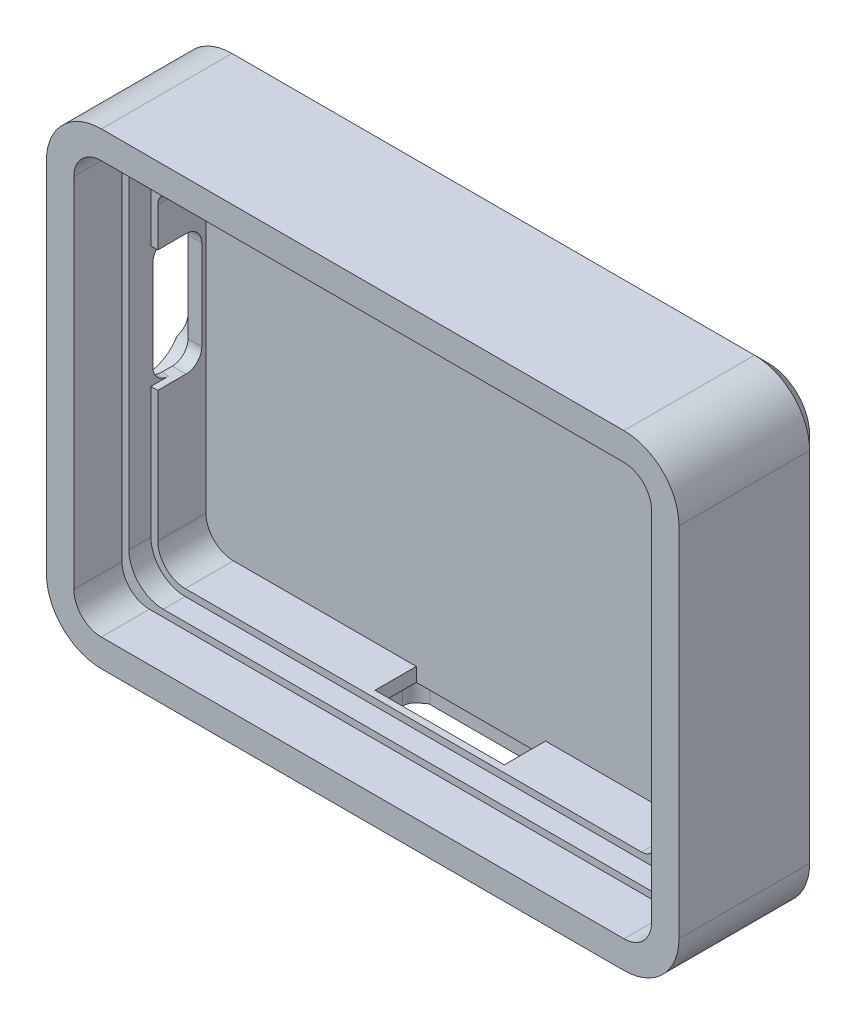
SolidWorks part; units mm, degrees
material "ABS"
ref_plane "前视基准面" through (0, 0, 0) normal (0, 0, 1) x (1, 0, 0)
ref_plane "上视基准面" through (0, 0, 0) normal (0, 1, 0) x (1, 0, 0)
ref_plane "右视基准面" through (0, 0, 0) normal (1, 0, 0) x (0, 0, -1)
other "Configuration Table"
sketch "草图1" plane through (0, 0, 0) normal (0, 0, 1) x (1, 0, 0)
  line L1 (-23, -17) -> (23, -17)
  line L2 (-23, -17) -> (-23, 17)
  line L3 (-23, 17) -> (23, 17)
  line L4 (23, -17) -> (23, 17)
  line L5 (-23, -17) -> (23, 17) construction
  line L6 (-23, 17) -> (23, -17) construction
  point P0 (0, 0)
  dimension "D1" = 46
  dimension "D2" = 34
extrude "凸台-拉伸1" add sketch "草图1" along normal blind 7
sketch "草图3" plane through (0, 0, 7) normal (0, 0, 1) x (1, 0, 0)
  line L1 (-18, -14) -> (18, -14)
  line L2 (-20, -12) -> (-20, 12)
  line L3 (-18, 14) -> (18, 14)
  line L4 (20, -12) -> (20, 12)
  line L5 (-20, -14) -> (20, 14) construction
  line L6 (-20, 14) -> (20, -14) construction
  arc A0 (18, 14) -> (20, 12) centre (18, 12) cw
  arc A1 (18, -14) -> (20, -12) centre (18, -12) ccw
  arc A2 (-18, -14) -> (-20, -12) centre (-18, -12) cw
  arc A3 (-20, 12) -> (-18, 14) centre (-18, 12) cw
  point P0 (0, 0)
  dimension "D3" = 2
  dimension "D1" = 40
  dimension "D2" = 28
extrude "切除-拉伸1" cut sketch "草图3" against normal blind 1.6
sketch "草图4" plane through (0, 0, 5.4) normal (0, 0, 1) x (1, 0, 0)
  line L4 (18, 14) -> (-18, 14)
  line L5 (-20, 12) -> (-20, -12)
  line L6 (-18, -14) -> (18, -14)
  line L7 (20, -12) -> (20, 12)
  line L8 (18, 14) -> (-18, 14)
  line L9 (-20, 12) -> (-20, -12)
  line L10 (-18, -14) -> (18, -14)
  line L11 (20, -12) -> (20, 12)
  circle A0 centre (-18, 12) radius 2
  circle A2 centre (18, -12) radius 2
  circle A3 centre (18, 12) radius 2
  arc A4 (20, 12) -> (18, 14) centre (18, 12) ccw
  arc A5 (-18, 14) -> (-20, 12) centre (-18, 12) ccw
  arc A6 (-20, -12) -> (-18, -14) centre (-18, -12) ccw
  arc A7 (18, -14) -> (20, -12) centre (18, -12) ccw
  arc A8 (20, 12) -> (18, 14) centre (18, 12) ccw
  arc A9 (-18, 14) -> (-20, 12) centre (-18, 12) ccw
  arc A10 (-20, -12) -> (-18, -14) centre (-18, -12) ccw
  arc A11 (18, -14) -> (20, -12) centre (18, -12) ccw
  line M10 (18, 14) -> (-18, 14)
  line M12 (-20, 12) -> (-20, -12)
  line M14 (-18, -14) -> (18, -14)
  line M16 (20, -12) -> (20, 12)
  dimension "D1" = 0
extrude "切除-拉伸2" cut sketch "草图4" against normal blind 3.5 contours A3 A0 A2 M10 M12 M14 M16 region at (-0.2097, -0.1398, 5.4)
fillet "圆角1" radius 1 6 edges at (20, -12, 3.65) (18, -14, 3.65) (18, 14, 3.65) (20, 12, 3.65) (-20, 12, 3.65) (-18, 14, 3.65)
fillet "圆角2" radius 4 4 edges at (23, -17, 3.5) (23, 17, 3.5) (-23, 17, 3.5) (-23, -17, 3.5)
sketch "草图5" plane through (0, 0, 5.4) normal (0, 0, 1) x (1, 0, 0)
  circle A0 centre (-18, 12) radius 0.85
  circle A1 centre (18, 12) radius 0.85
  circle A2 centre (18, -12) radius 0.85
  dimension "D2" = 1.7
  dimension "D3" = 1.7
  dimension "D4" = 1.7
extrude "切除-拉伸3" cut sketch "草图5" against normal blind 4
sketch "草图6" plane through (-23, 0, 0) normal (-1, 0, 0) x (0, 0, 1)
  line L0 (3.35, -2.515) -> (4.11, -2.515) construction
  line L1 (5.26, -1.365) -> (5.26, 5.175) construction
  line L2 (4.11, 6.325) -> (3.35, 6.325) construction
  line L3 (2.2, 5.175) -> (2.2, -1.365) construction
  line L4 (3.35, -2.515) -> (4.11, -2.515)
  line L5 (5.26, -1.365) -> (5.26, 5.175)
  line L6 (4.11, 6.325) -> (3.35, 6.325)
  line L7 (2.2, 5.175) -> (2.2, -1.365)
  line L8 (3.35, -4.015) -> (4.11, -4.015)
  line L9 (6.76, -1.365) -> (6.76, 5.175)
  line L10 (4.11, 7.825) -> (3.35, 7.825)
  line L11 (0.7, 5.175) -> (0.7, -1.365)
  arc A0 (2.2, -1.365) -> (3.35, -2.515) centre (3.35, -1.365) ccw construction
  arc A1 (4.11, -2.515) -> (5.26, -1.365) centre (4.11, -1.365) ccw construction
  arc A2 (5.26, 5.175) -> (4.11, 6.325) centre (4.11, 5.175) ccw construction
  arc A3 (3.35, 6.325) -> (2.2, 5.175) centre (3.35, 5.175) ccw construction
  arc A4 (2.2, -1.365) -> (3.35, -2.515) centre (3.35, -1.365) ccw
  arc A5 (4.11, -2.515) -> (5.26, -1.365) centre (4.11, -1.365) ccw
  arc A6 (5.26, 5.175) -> (4.11, 6.325) centre (4.11, 5.175) ccw
  arc A7 (3.35, 6.325) -> (2.2, 5.175) centre (3.35, 5.175) ccw
  arc A8 (4.11, -4.015) -> (6.76, -1.365) centre (4.11, -1.365) ccw
  arc A9 (6.76, 5.175) -> (4.11, 7.825) centre (4.11, 5.175) ccw
  arc A10 (3.35, 7.825) -> (0.7, 5.175) centre (3.35, 5.175) ccw
  arc A11 (0.7, -1.365) -> (3.35, -4.015) centre (3.35, -1.365) ccw
  dimension "D1" = 1.5
extrude "切除-拉伸4" cut sketch "草图6" against normal up to next contours L6 A7 L7 A4 L4 A5 L5 A6 region at (-23, 1.905, 3.73)
extrude "切除-拉伸5" cut sketch "草图6<3>" against normal blind 2
sketch "草图6<3>" plane through (-23, 0, 0) normal (-1, 0, 0) x (0, 0, 1) same geometry as "草图6"
sketch "草图7" plane through (0, -17, 0) normal (0, -1, 0) x (1, 0, 0)
  line L1 (4.7, 1.9) -> (-4.7, 1.9)
  line L2 (4.7, 1.9) -> (4.7, 4.9)
  line L3 (4.7, 4.9) -> (-4.7, 4.9)
  line L4 (-4.7, 1.9) -> (-4.7, 4.9)
  line L5 (23, 7) -> (23, 0) construction
  line L6 (-23, 0) -> (-23, 7) construction
  line L7 (-19, 7) -> (19, 7) construction
  line L8 (-19, 0) -> (19, 0) construction
  dimension "D1" = 18.3
  dimension "D2" = 18.3
  dimension "D3" = 2.1
  dimension "D4" = 1.9
extrude "切除-拉伸6" cut sketch "草图7" against normal blind 3
sketch "草图8" plane through (0, -17, 0) normal (0, -1, 0) x (1, 0, 0)
  line L0 (4.7, 1.9) -> (4.7, 4.9) construction
  line L1 (4.7, 4.9) -> (-4.7, 4.9) construction
  line L2 (-4.7, 4.9) -> (-4.7, 1.9) construction
  line L3 (-4.7, 1.9) -> (4.7, 1.9) construction
  line L4 (4.7, 1.9) -> (4.7, 4.9)
  line L5 (4.7, 4.9) -> (-4.7, 4.9)
  line L6 (-4.7, 4.9) -> (-4.7, 1.9)
  line L7 (-4.7, 1.9) -> (4.7, 1.9)
  line L8 (5.7, 0.9) -> (5.7, 5.9)
  line L9 (5.7, 5.9) -> (-5.7, 5.9)
  line L10 (-5.7, 5.9) -> (-5.7, 0.9)
  line L11 (-5.7, 0.9) -> (5.7, 0.9)
  dimension "D1" = 1
extrude "切除-拉伸7" cut sketch "草图8" against normal blind 2
fillet "圆角3" radius 1 4 edges at (5.7, -16, 5.9) (5.7, -16, 0.9) (-5.7, -16, 0.9) (-5.7, -16, 5.9)
sketch "草图9" plane through (0, 0, 7) normal (0, 0, 1) x (1, 0, 0)
  line L0 (-19, -15) -> (19, -15)
  line L1 (21, -13) -> (21, 13)
  line L2 (19, 15) -> (-19, 15)
  line L3 (-21, 13) -> (-21, -13)
  line L4 (-19, -17) -> (19, -17)
  line L5 (23, -13) -> (23, 13)
  line L6 (19, 17) -> (-19, 17)
  line L7 (-23, 13) -> (-23, -13)
  line L8 (-19, -17) -> (19, -17)
  line L9 (23, -13) -> (23, 13)
  line L10 (19, 17) -> (-19, 17)
  line L11 (-23, 13) -> (-23, -13)
  arc A0 (19, -15) -> (21, -13) centre (19, -13) ccw
  arc A1 (21, 13) -> (19, 15) centre (19, 13) ccw
  arc A2 (-19, 15) -> (-21, 13) centre (-19, 13) ccw
  arc A3 (-21, -13) -> (-19, -15) centre (-19, -13) ccw
  arc A4 (19, -17) -> (23, -13) centre (19, -13) ccw
  arc A5 (23, 13) -> (19, 17) centre (19, 13) ccw
  arc A6 (-19, 17) -> (-23, 13) centre (-19, 13) ccw
  arc A7 (-23, -13) -> (-19, -17) centre (-19, -13) ccw
  arc A8 (19, -17) -> (23, -13) centre (19, -13) ccw
  arc A9 (23, 13) -> (19, 17) centre (19, 13) ccw
  arc A10 (-19, 17) -> (-23, 13) centre (-19, 13) ccw
  arc A11 (-23, -13) -> (-19, -17) centre (-19, -13) ccw
  dimension "D1" = 0
  dimension "D2" = 2
extrude "凸台-拉伸2" add sketch "草图9" along normal blind 3.5
chamfer "倒角1" distance 1 angle 45 8 edges at (21.8284, 15.8284, 0) (0, 17, 0) (-21.8284, 15.8284, 0) (-23, 0, 0) (-21.8284, -15.8284, 0) (0, -17, 0) (21.8284, -15.8284, 0) (23, 0, 0)
sketch "草图10" plane through (0, 0, 7) normal (0, 0, 1) x (1, 0, 0)
  line L0 (20, -12) -> (20, 12) construction
  line L1 (-18, -14) -> (18, -14) construction
  line L2 (-20, 9.1716) -> (-20, 12) construction
  line L3 (-20, 9.1716) -> (-20, -12) construction
  line L4 (-21, 13) -> (-21, -13)
  line L5 (-19, -15) -> (19, -15)
  line L6 (21, -13) -> (21, 13)
  line L7 (19, 15) -> (-19, 15)
  line L8 (-21, 13) -> (-21, -13)
  line L9 (-19, -15) -> (19, -15)
  line L10 (21, -13) -> (21, 13)
  line L11 (19, 15) -> (-19, 15)
  line L12 (18, 14) -> (-18, 14) construction
  line L13 (20, -12) -> (20, 12)
  line L14 (-18, -14) -> (18, -14)
  line L15 (-20, 9.1716) -> (-20, 12)
  line L16 (-20, 9.1716) -> (-20, -12)
  line L17 (18, 14) -> (-18, 14)
  line L18 (20.5, -12) -> (20.5, 12)
  line L19 (18, 14.5) -> (-18, 14.5)
  line L20 (-20.5, 9.1716) -> (-20.5, 12)
  line L21 (-20.5, 9.1716) -> (-20.5, -12)
  line L22 (-18, -14.5) -> (18, -14.5)
  arc A0 (20, 12) -> (18, 14) centre (18, 12) ccw construction
  arc A1 (18, -14) -> (20, -12) centre (18, -12) ccw construction
  arc A2 (-20, -12) -> (-18, -14) centre (-18, -12) ccw construction
  arc A3 (-18, 14) -> (-20, 12) centre (-18, 12) ccw construction
  arc A4 (-21, -13) -> (-19, -15) centre (-19, -13) ccw
  arc A5 (19, -15) -> (21, -13) centre (19, -13) ccw
  arc A6 (21, 13) -> (19, 15) centre (19, 13) ccw
  arc A7 (-19, 15) -> (-21, 13) centre (-19, 13) ccw
  arc A8 (-21, -13) -> (-19, -15) centre (-19, -13) ccw
  arc A9 (19, -15) -> (21, -13) centre (19, -13) ccw
  arc A10 (21, 13) -> (19, 15) centre (19, 13) ccw
  arc A11 (-19, 15) -> (-21, 13) centre (-19, 13) ccw
  arc A12 (20, 12) -> (18, 14) centre (18, 12) ccw
  arc A13 (18, -14) -> (20, -12) centre (18, -12) ccw
  arc A14 (-20, -12) -> (-18, -14) centre (-18, -12) ccw
  arc A15 (-18, 14) -> (-20, 12) centre (-18, 12) ccw
  arc A16 (20.5, 12) -> (18, 14.5) centre (18, 12) ccw
  arc A17 (-18, 14.5) -> (-20.5, 12) centre (-18, 12) ccw
  arc A18 (-20.5, -12) -> (-18, -14.5) centre (-18, -12) ccw
  arc A19 (18, -14.5) -> (20.5, -12) centre (18, -12) ccw
  line M26 (-18, 14) -> (18, 14)
  arc M27 (18, 14) -> (20, 12) centre (18, 12) cw
  line M28 (20, 12) -> (20, -12)
  arc M29 (20, -12) -> (18, -14) centre (18, -12) cw
  line M30 (18, -14) -> (-18, -14)
  arc M31 (-18, -14) -> (-20, -12) centre (-18, -12) cw
  line M32 (-20, -12) -> (-20, 12)
  arc M33 (-20, 12) -> (-18, 14) centre (-18, 12) cw
  dimension "D1" = 0
  dimension "D2" = 0.5
extrude "切除-拉伸9" cut sketch "草图10" against normal up to surface (1.6 mm away) contours L22 A19 L18 A16 L19 A17 L20 L21 A18 M33 M26 M27 M28 M29 M30 M31 M32 | A12 L17 A15 L15 L16 A14 L14 A13 L13 region at (19.7323, -13.7323, 7) up to face at (-17.15, 12, 5.4)
sketch "草图11" plane through (0, 0, 5.4) normal (0, 0, 1) x (1, 0, 0)
  line L0 (-20.5, -12) -> (-20.5, 12) construction
  line L1 (-20.5, 6.325) -> (-20, 6.325)
  line L2 (-20.5, 6.325) -> (-20.5, -2.515)
  line L3 (-20.5, -2.515) -> (-20, -2.515)
  line L4 (-20, 6.325) -> (-20, -2.515)
  line L5 (-20, 9.1716) -> (-20, -12) construction
extrude "切除-拉伸10" cut sketch "草图11" against normal up to next
sketch "草图12" plane through (-23, 0, 0) normal (-1, 0, 0) x (0, 0, 1)
  line L8 (0.6, 5.175) -> (0.6, -1.365)
  line L9 (3.35, -4.115) -> (4.11, -4.115)
  line L10 (6.86, -1.365) -> (6.86, 5.175)
  line L11 (4.11, 7.925) -> (3.35, 7.925)
  line L12 (0.6, 5.175) -> (0.6, -1.365)
  line L13 (3.35, -4.115) -> (4.11, -4.115)
  line L14 (6.86, -1.365) -> (6.86, 5.175)
  line L15 (4.11, 7.925) -> (3.35, 7.925)
  arc A8 (0.6, -1.365) -> (3.35, -4.115) centre (3.35, -1.365) ccw
  arc A9 (4.11, -4.115) -> (6.86, -1.365) centre (4.11, -1.365) ccw
  arc A10 (6.86, 5.175) -> (4.11, 7.925) centre (4.11, 5.175) ccw
  arc A11 (3.35, 7.925) -> (0.6, 5.175) centre (3.35, 5.175) ccw
  arc A12 (0.6, -1.365) -> (3.35, -4.115) centre (3.35, -1.365) ccw
  arc A13 (4.11, -4.115) -> (6.86, -1.365) centre (4.11, -1.365) ccw
  arc A14 (6.86, 5.175) -> (4.11, 7.925) centre (4.11, 5.175) ccw
  arc A15 (3.35, 7.925) -> (0.6, 5.175) centre (3.35, 5.175) ccw
  dimension "D1" = 0.1
extrude "切除-拉伸11" cut sketch "草图12" against normal up to surface (2 mm away) up to face at (-21, 1.905, 3.73)
